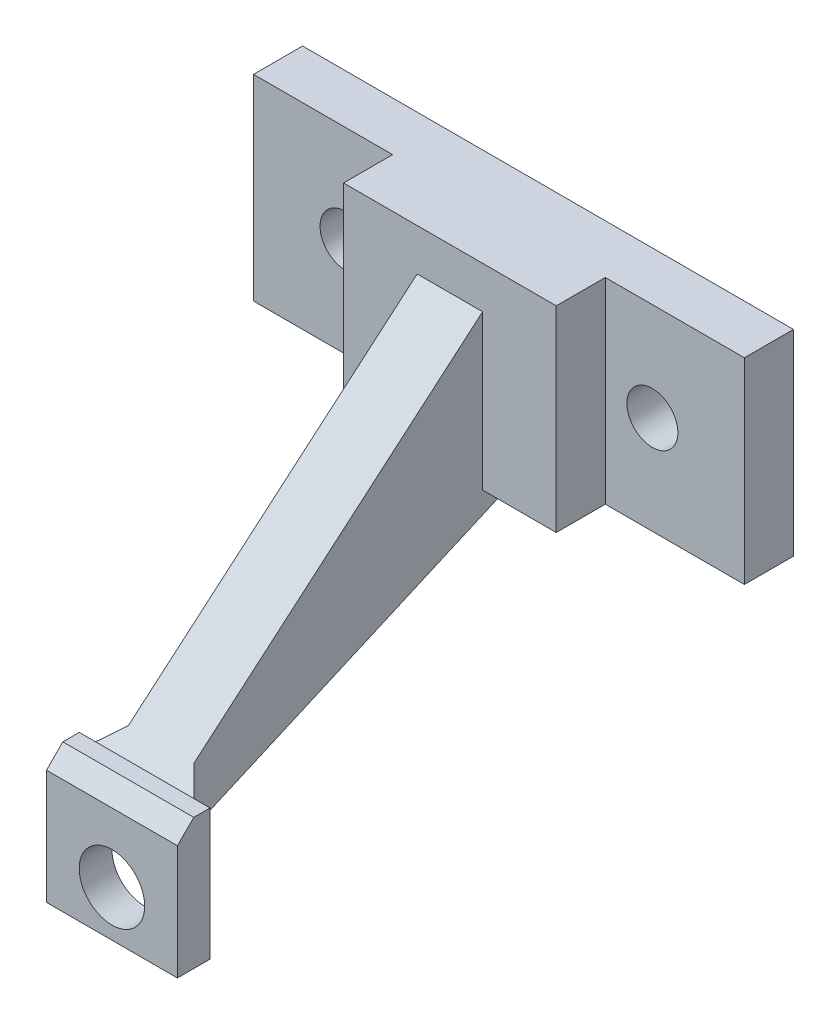
SolidWorks part; units mm, degrees
ref_plane "前视基准面" through (0, 0, 0) normal (0, 0, 1) x (1, 0, 0)
ref_plane "上视基准面" through (0, 0, 0) normal (0, 1, 0) x (1, 0, 0)
ref_plane "右视基准面" through (0, 0, 0) normal (1, 0, 0) x (0, 0, -1)
other "Configuration Table"
sketch "草图1" plane through (0, 0, 0) normal (0, 0, 1) x (1, 0, 0)
  line L0 (0, 12) -> (11.25, 0) construction
  line L1 (0, 0) -> (30, 0)
  line L2 (0, 0) -> (0, 12)
  line L3 (0, 12) -> (30, 12)
  line L4 (30, 0) -> (30, 12)
  line L5 (30, 12) -> (18.75, 0) construction
  line L6 (0, 0) -> (11.25, 12) construction
  line L7 (30, 0) -> (18.75, 12) construction
  circle A0 centre (5.625, 6) radius 1.56
  circle A1 centre (24.375, 6) radius 1.56
  dimension "D5" = 3.12
  dimension "D6" = 3.12
  dimension "D1" = 30
  dimension "D2" = 12
  dimension "D3" = 11.25
  dimension "D4" = 11.25
extrude "凸台-拉伸1" add sketch "草图1" along normal blind 3
sketch "草图2" plane through (0, 0, 3) normal (0, 0, 1) x (1, 0, 0)
  line L0 (0, 12) -> (8.5, 8.6) construction
  line L1 (0, 0) -> (8.5, 3.4) construction
  line L3 (0, 0) -> (30, 0) construction
  line L5 (8.5, 12) -> (8.5, 0)
  line L6 (8.5, 12) -> (21.5, 12)
  line L8 (8.5, 0) -> (21.5, 0)
  line L9 (21.5, 12) -> (21.5, 0)
  line L10 (21.5, 8.6) -> (30, 12) construction
  line L11 (21.5, 3.4) -> (30, 0) construction
extrude "凸台-拉伸2" add sketch "草图2" along normal blind 3
ref_plane "基准面1" through (15, 0, 0) normal (1, 0, 0) x (0, 0, -1)
sketch "草图4" plane through (15, 0, 0) normal (1, 0, 0) x (0, 0, -1)
  line L0 (997, 6) -> (-3, 6) construction
  line L1 (-3, 0) -> (-24.6506, -9.5)
  line L3 (-3, 12) -> (-3, 0) construction
  line L4 (-3, 6) -> (-3, 0)
  line L5 (-24.6506, -9.5) -> (-24.6506, -6.5)
  line L6 (-3, 6) -> (-3, 12)
  line L7 (-3, 12) -> (-24.6506, -6.5)
  line L8 (-10.0218, 6) -> (-1014.4282, 6) construction
  dimension "D2" = 25
  dimension "D3" = 3
ref_plane "基准面2" through (0, 0, 24.6506) normal (0, 0, 1) x (1, 0, 0)
extrude "凸台-拉伸3" add sketch "草图4" along normal blind 2 and the other way blind 2
sketch "草图8" plane through (0, 0, 24.6506) normal (0, 0, 1) x (1, 0, 0)
  line L1 (19, -6.5) -> (11, -6.5)
  line L3 (19, -14.5) -> (11, -14.5)
  line L4 (11, -6.5) -> (11, -14.5)
  line L5 (15, -11.825) -> (15, 11.825) construction
  line L6 (19, -6.5) -> (19, -14.5)
  line L7 (15, -6.5) -> (15, -14.5) construction
  circle A0 centre (15, -11.7) radius 2
  dimension "D3" = 4
  dimension "D1" = 8
  dimension "D2" = 2.8
extrude "凸台-拉伸4" add sketch "草图8" along normal blind 2
chamfer "倒角3" distance 1 angle 45 3 edges at (17, -8, 24.6506) (15, -9.5, 24.6506) (13, -8, 24.6506) first distance on face at (17, -1.3127, 12.8603) first distance on face at (15, -4.75, 13.8253) first distance on face at (13, -1.3127, 12.8603)
chamfer "倒角6" distance 1 angle 45 1 edges at (15, -6.5, 26.6506)
